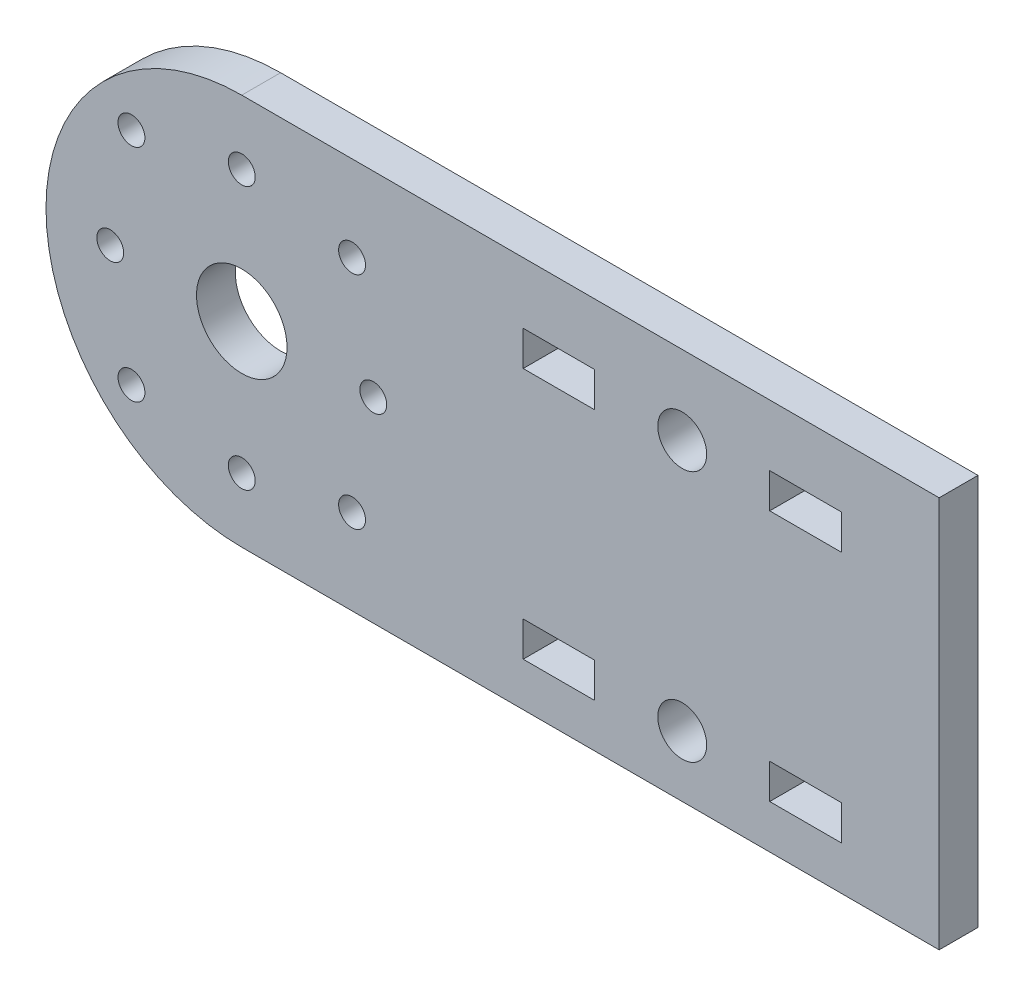
SolidWorks part; units mm, degrees
ref_plane "Front Plane" through (0, 0, 0) normal (0, 0, 1) x (1, 0, 0)
ref_plane "Top Plane" through (0, 0, 0) normal (0, 1, 0) x (1, 0, 0)
ref_plane "Right Plane" through (0, 0, 0) normal (1, 0, 0) x (0, 0, -1)
sketch "Sketch1" plane through (0, 0, 0) normal (0, 0, 1) x (1, 0, 0)
  line L1 (19, 0) -> (76, 0)
  line L2 (42, 27) -> (47.85, 27)
  line L3 (19, 32) -> (76, 32)
  line L4 (76, 0) -> (76, 32)
  line L5 (42, 27) -> (42, 24.15)
  line L6 (42, 24.15) -> (47.85, 24.15)
  line L7 (47.85, 27) -> (47.85, 24.15)
  line L8 (62.15, 27) -> (68, 27)
  line L9 (62.15, 27) -> (62.15, 24.15)
  line L10 (62.15, 24.15) -> (68, 24.15)
  line L11 (68, 27) -> (68, 24.15)
  line L12 (47.85, 6.425) -> (42, 6.425)
  line L13 (47.85, 6.425) -> (47.85, 3.575)
  line L14 (47.85, 3.575) -> (42, 3.575)
  line L15 (42, 6.425) -> (42, 3.575)
  line L16 (62.15, 6.425) -> (68, 6.425)
  line L17 (62.15, 6.425) -> (62.15, 3.575)
  line L18 (62.15, 3.575) -> (68, 3.575)
  line L19 (68, 6.425) -> (68, 3.575)
  arc A0 (19, 32) -> (19, 0) centre (19, 16) ccw
  circle A1 centre (8.25, 16) radius 1.1
  circle A2 centre (9.9844, 25.0156) radius 1.1
  circle A3 centre (28.0156, 25.0156) radius 1.1
  circle A4 centre (28.0156, 6.9844) radius 1.1
  circle A5 centre (9.9844, 6.9844) radius 1.1
  circle A6 centre (19, 26.75) radius 1.1
  circle A7 centre (29.75, 16) radius 1.1
  circle A8 centre (19, 5.25) radius 1.1
  circle A9 centre (19, 16) radius 3.7
  circle A10 centre (55, 5) radius 2
  circle A18 centre (55, 25.575) radius 2
  point P17 (19, 16)
  point P22 (19, 16)
  point P25 (19, 16)
  point P26 (19, 16)
  dimension "D3" = 19
  dimension "D6" = 12.75
  dimension "D7" = 2.2
  dimension "D8" = 45
  dimension "D10" = 5
  dimension "D22" = 1.425
  dimension "D23" = 4
  dimension "D4" = 2.2
  dimension "D5" = 10.75
  dimension "D9" = 7.4
  dimension "D11" = 4
  dimension "D1" = 32
  dimension "D12" = 2.85
  dimension "D13" = 1.425
  dimension "D14" = 5.85
  dimension "D15" = 5.85
  dimension "D16" = 26
  dimension "D17" = 2.85
  dimension "D18" = 2.85
  dimension "D19" = 8
  dimension "D20" = 5
  dimension "D21" = 13
  dimension "D24" = 76
extrude "Boss-Extrude1" add sketch "Sketch1" along normal blind 3.175
